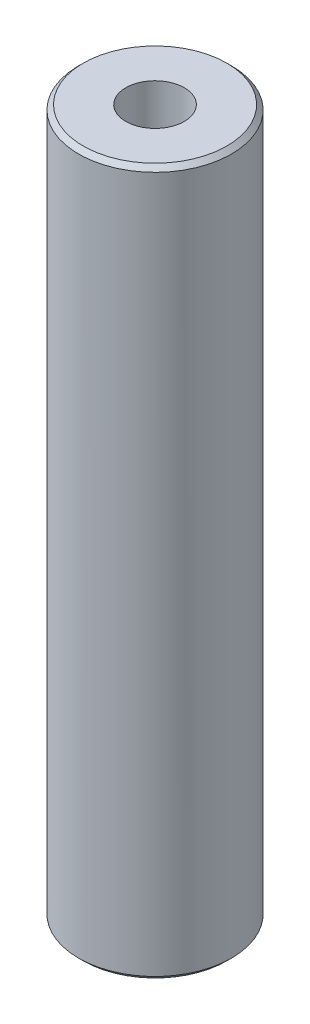
SolidWorks part; units mm, degrees
ref_plane "Front Plane" through (0, 0, 0) normal (0, 0, 1) x (1, 0, 0)
ref_plane "Top Plane" through (0, 0, 0) normal (0, 1, 0) x (1, 0, 0)
ref_plane "Right Plane" through (0, 0, 0) normal (1, 0, 0) x (0, 0, -1)
sketch "Sketch1" plane through (0, 0, 0) normal (0, 1, 0) x (1, 0, 0)
  circle A0 centre (0, 0) radius 40
  dimension "SHAFT_OD" = 80
extrude "Boss-Extrude1" add sketch "Sketch1" along normal blind 369.1998
sketch "Sketch2" plane through (0, 0, 0) normal (0, 1, 0) x (1, 0, 0)
  circle A0 centre (0, 0) radius 15.302
  dimension "BORE_D" = 30.604
extrude "Cut-Extrude1" cut sketch "Sketch2" along normal through all
chamfer "Chamfer1" distance 2.4206 angle 45 2 edges at (0, 369.1998, 40) (0, 0, 40)
